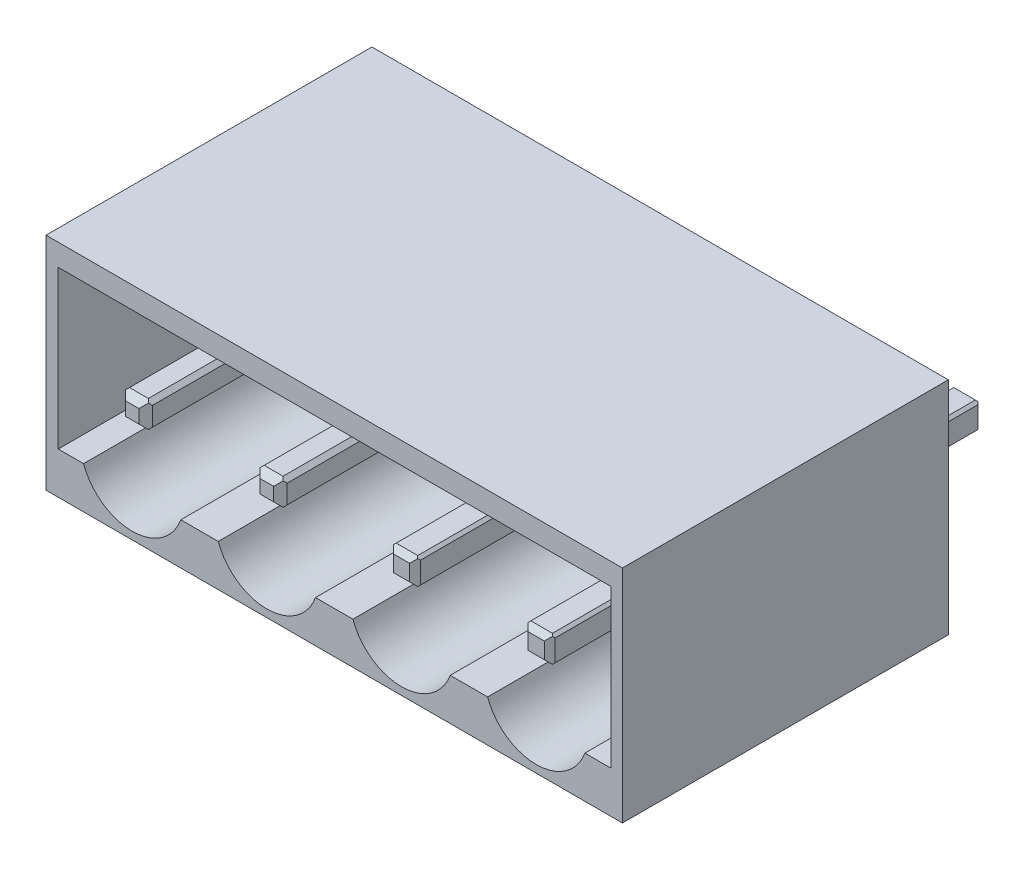
SolidWorks part; units mm, degrees
ref_plane "Спереди" through (0, 0, 0) normal (0, 0, 1) x (1, 0, 0)
ref_plane "Сверху" through (0, 0, 0) normal (0, 1, 0) x (1, 0, 0)
ref_plane "Справа" through (0, 0, 0) normal (1, 0, 0) x (0, 0, -1)
sketch "Эскиз1" plane through (0, 0, 0) normal (0, 0, 1) x (1, 0, 0)
  line L1 (-10.7, 4.1) -> (10.7, 4.1)
  line L2 (-10.7, 4.1) -> (-10.7, -4.1)
  line L3 (-10.7, -4.1) -> (10.7, -4.1)
  line L4 (10.7, 4.1) -> (10.7, -4.1)
  line L5 (-10.7, 4.1) -> (10.7, -4.1) construction
  line L6 (-10.7, -4.1) -> (10.7, 4.1) construction
  point P0 (0, 0)
  dimension "D1" = 8.2
  dimension "D2" = 21.4
extrude "Бобышка-Вытянуть1" add sketch "Эскиз1" along normal blind 12.1
sketch "Эскиз4" plane through (0, 0, 12.1) normal (0, 0, 1) x (1, 0, 0)
  circle A0 centre (-7.5, 0) radius 1.25
  circle A1 centre (-2.5, 0) radius 1.25
  circle A2 centre (2.5, 0) radius 1.25
  circle A3 centre (7.5, 0) radius 1.25
  dimension "D1" = 2.5
  dimension "D2" = 3.2
  dimension "D5" = 2
  dimension "D3" = 2
  dimension "D4" = 2
extrude "Вырез-Вытянуть3" cut sketch "Эскиз4" against normal blind 8
sketch "Эскиз5" plane through (0, 0, 12.1) normal (0, 0, 1) x (1, 0, 0)
  line L0 (-10.2456, 0) -> (-10.2456, 3.2929)
  line L1 (-10.2456, 3.2929) -> (0.2785, 3.2929)
  line L4 (-10.2456, -2.549) -> (-10.2456, 0)
  line L5 (-0.6942, -2.549) -> (0.6942, -2.549)
  line L6 (-9.3058, -2.549) -> (-10.2456, -2.549)
  line L7 (-5.6942, -2.549) -> (-4.3058, -2.549)
  line L11 (0.2785, 3.2929) -> (5.2785, 3.2929)
  line L12 (9.3058, -2.549) -> (10.2785, -2.549)
  line L13 (-0.6942, -2.549) -> (0.6942, -2.549) [skipped]
  line L14 (10.2785, 3.2929) -> (10.2785, -2.549)
  line L15 (4.3058, -2.549) -> (5.6942, -2.549)
  line L16 (5.2785, 3.2929) -> (10.2785, 3.2929)
  arc A1 (0.6942, -2.549) -> (4.3058, -2.549) centre (2.5, -1.9) ccw
  arc A2 (5.6942, -2.549) -> (9.3058, -2.549) centre (7.5, -1.9) ccw
  arc A5 (-9.3058, -2.549) -> (-5.6942, -2.549) centre (-7.5, -1.9) ccw
  arc A6 (-4.3058, -2.549) -> (-0.6942, -2.549) centre (-2.5, -1.9) ccw
  dimension "D1" = 3.2
  dimension "D2" = 2.2
  dimension "D3" = 2
  dimension "D4" = 2
  dimension "D5" = 2
extrude "Вырез-Вытянуть4" cut sketch "Эскиз5" against normal blind 7.8
sketch "Эскиз7" plane through (0, 0, 4.1) normal (0, 0, 1) x (1, 0, 0)
  line L0 (-3, 0.5) -> (-2, 0.5)
  line L1 (-8, 0.5) -> (-7, 0.5)
  line L2 (-8, 0.5) -> (-8, -0.5)
  line L3 (-8, -0.5) -> (-7, -0.5)
  line L4 (-7, 0.5) -> (-7, -0.5)
  line L5 (-8, 0.5) -> (-7, -0.5) construction
  line L6 (-8, -0.5) -> (-7, 0.5) construction
  line L7 (-3, 0.5) -> (-3, -0.5)
  line L8 (-3, -0.5) -> (-2, -0.5)
  line L9 (-2, 0.5) -> (-2, -0.5)
  line L10 (-3, 0.5) -> (-2, -0.5) construction
  line L11 (-3, -0.5) -> (-2, 0.5) construction
  line L12 (2, 0.5) -> (3, 0.5)
  line L13 (2, 0.5) -> (2, -0.5)
  line L14 (2, -0.5) -> (3, -0.5)
  line L15 (3, 0.5) -> (3, -0.5)
  line L16 (2, 0.5) -> (3, -0.5) construction
  line L17 (2, -0.5) -> (3, 0.5) construction
  line L18 (7, 0.5) -> (8, 0.5)
  line L19 (7, 0.5) -> (7, -0.5)
  line L20 (7, -0.5) -> (8, -0.5)
  line L21 (8, 0.5) -> (8, -0.5)
  line L22 (7, 0.5) -> (8, -0.5) construction
  line L23 (7, -0.5) -> (8, 0.5) construction
  point P0 (-7.5, 0)
  point P7 (-2.5, 0)
  point P12 (2.5, 0)
  point P17 (7.5, 0)
  dimension "D1" = 1
  dimension "D2" = 1
  dimension "D3" = 2
  dimension "D4" = 2
  dimension "D5" = 2
extrude "Бобышка-Вытянуть2" add sketch "Эскиз7" along normal blind 8
chamfer "Фаска1" distance 0.15 angle 45 8 edges at (-3, -0.5, 8.1) (-3, 0.5, 8.1) (-2, 0.5, 8.1) (-2, -0.5, 8.1) (-7, -0.5, 8.1) (-7, 0.5, 8.1) (-8, -0.5, 8.1) (-8, 0.5, 8.1)
chamfer "Фаска2" distance 0.25 angle 45 8 edges at (-3, 0, 12.1) (-2.5, 0.5, 12.1) (-2, 0, 12.1) (-2.5, -0.5, 12.1) (-7, 0, 12.1) (-7.5, -0.5, 12.1) (-8, 0, 12.1) (-7.5, 0.5, 12.1)
sketch "Эскиз8" plane through (0, -4.1, 0) normal (0, 0, 1) x (-1, 0, 0)
  line L0 (3, -4.25) -> (2, -4.25)
  line L1 (8, -4.25) -> (7, -4.25)
  line L2 (8, -4.25) -> (8, -3.25)
  line L3 (8, -3.25) -> (7, -3.25)
  line L4 (7, -4.25) -> (7, -3.25)
  line L5 (8, -4.25) -> (7, -3.25) construction
  line L6 (8, -3.25) -> (7, -4.25) construction
  line L7 (3, -4.25) -> (3, -3.25)
  line L8 (3, -3.25) -> (2, -3.25)
  line L9 (2, -4.25) -> (2, -3.25)
  line L10 (3, -4.25) -> (2, -3.25) construction
  line L11 (3, -3.25) -> (2, -4.25) construction
  line L12 (-2, -4.25) -> (-3, -4.25)
  line L13 (-2, -4.25) -> (-2, -3.25)
  line L14 (-2, -3.25) -> (-3, -3.25)
  line L15 (-3, -4.25) -> (-3, -3.25)
  line L16 (-2, -4.25) -> (-3, -3.25) construction
  line L17 (-2, -3.25) -> (-3, -4.25) construction
  line L18 (-7, -4.25) -> (-8, -4.25)
  line L19 (-7, -4.25) -> (-7, -3.25)
  line L20 (-7, -3.25) -> (-8, -3.25)
  line L21 (-8, -4.25) -> (-8, -3.25)
  line L22 (-7, -4.25) -> (-8, -3.25) construction
  line L23 (-7, -3.25) -> (-8, -4.25) construction
  point P0 (7.5, -3.75)
  point P7 (2.5, -3.75)
  point P12 (-2.5, -3.75)
  point P18 (-7.5, -3.75)
  dimension "D1" = 1
  dimension "D2" = 1
  dimension "D3" = 3.2
  dimension "D4" = 4.45
  dimension "D5" = 2
  dimension "D6" = 2
  dimension "D7" = 2
extrude "Бобышка-Вытянуть3" add sketch "Эскиз8" against normal blind 4
chamfer "Фаска6" distance 0.1 angle 45 4 edges at (2, -0.5, 8.1) (3, -0.5, 8.1) (3, 0.5, 8.1) (2, 0.5, 8.1)
chamfer "Фаска7" distance 0.2 angle 45 4 edges at (3, 0, 12.1) (2.5, -0.5, 12.1) (2, 0, 12.1) (2.5, 0.5, 12.1)
chamfer "Фаска10" distance 0.1 angle 45 12 edges at (-8, -0.85, -2) (-8, 0.15, -2) (-3, -0.85, -2) (-3, 0.15, -2) (2, -0.85, -2) (2, 0.15, -2) (-7, -0.85, -2) (-2, -0.85, -2) (3, -0.85, -2) (-7, 0.15, -2) (-2, 0.15, -2) (3, 0.15, -2)
chamfer "Фаска11" distance 0.2 angle 45 12 edges at (-7, -0.35, -4) (-7.5, 0.15, -4) (-8, -0.35, -4) (-7.5, -0.85, -4) (-2.5, -0.85, -4) (-3, -0.35, -4) (-2.5, 0.15, -4) (-2, -0.35, -4) (2, -0.35, -4) (2.5, 0.15, -4) (3, -0.35, -4) (2.5, -0.85, -4)
chamfer "Фаска12" distance 0.1 angle 45 4 edges at (7, 0.15, -2) (7, -0.85, -2) (8, 0.15, -2) (8, -0.85, -2)
chamfer "Фаска13" distance 0.2 angle 45 4 edges at (7.5, 0.15, -4) (8, -0.35, -4) (7, -0.35, -4) (7.5, -0.85, -4)
chamfer "Фаска14" distance 0.1 angle 45 4 edges at (8, 0.5, 8.1) (8, -0.5, 8.1) (7, -0.5, 8.1) (7, 0.5, 8.1)
chamfer "Фаска15" distance 0.2 angle 45 4 edges at (7, 0, 12.1) (7.5, -0.5, 12.1) (8, 0, 12.1) (7.5, 0.5, 12.1)
